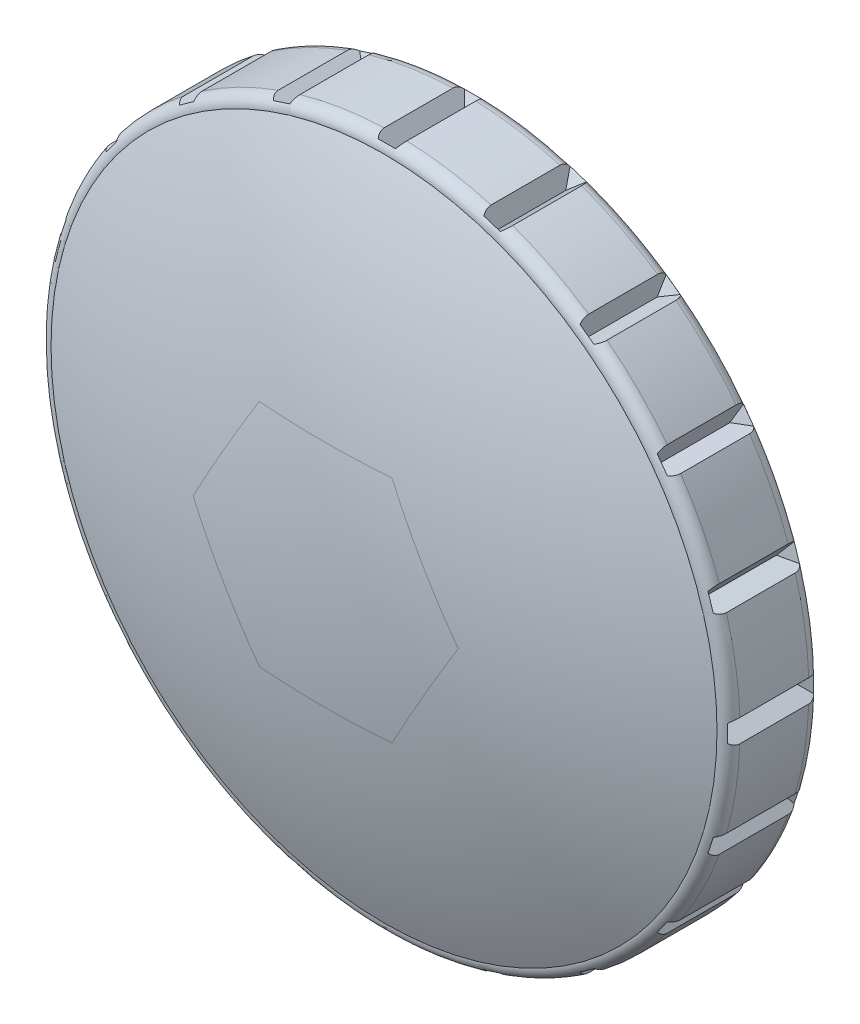
SolidWorks part; units mm, degrees
ref_plane "Front Plane" through (0, 0, 0) normal (0, 0, 1) x (1, 0, 0)
ref_plane "Top Plane" through (0, 0, 0) normal (0, 1, 0) x (1, 0, 0)
ref_plane "Right Plane" through (0, 0, 0) normal (1, 0, 0) x (0, 0, -1)
sketch "Sketch1" plane through (0, 0, 0) normal (0, 0, 1) x (1, 0, 0)
  circle A0 centre (0, 0) radius 38.1
  dimension "D1" = 76.2
extrude "Boss-Extrude1" add sketch "Sketch1" along normal mid plane 10.16
fillet "Fillet1" radius 1.27 2 edges at (38.1, 0, -5.08) (38.1, 0, 5.08)
ref_plane "Plane1" through (0, 38.1, 0) normal (0, 1, 0) x (1, 0, 0)
sketch "Sketch2" plane through (0, 38.1, 0) normal (0, 1, 0) x (1, 0, 0)
  line L0 (-36.83, -5.08) -> (36.83, -5.08) construction
  line L1 (-1.27, 5.08) -> (1.27, 5.08)
  line L2 (-1.27, 5.08) -> (-1.27, -5.08)
  line L3 (-1.27, -5.08) -> (1.27, -5.08)
  line L4 (1.27, 5.08) -> (1.27, -5.08)
  line L5 (-1.27, 5.08) -> (1.27, -5.08) construction
  line L6 (-1.27, -5.08) -> (1.27, 5.08) construction
  line L7 (36.83, 5.08) -> (-36.83, 5.08) construction
  point P0 (0, 0)
  dimension "D1" = 2.54
extrude "Cut-Extrude1" cut sketch "Sketch2" against normal blind 2.54 draft 35
pattern_circular "CirPattern1" count 20 over 360 about axis through (0, 0, 3.81) along (0, 0, -1) of "Cut-Extrude1"
dome "Dome1" faces to dome 1 distance 7.62 reverse direction no elliptical dome no face at (36.83, 0, 5.08) parameters "D1"=7.62
sketch "Sketch3" plane through (0, 0, -5.08) normal (0, 0, -1) x (-1, 0, 0)
  line L1 (30.7959, 0) -> (15.3979, 26.67)
  line L2 (15.3979, 26.67) -> (-15.3979, 26.67)
  line L3 (-15.3979, 26.67) -> (-30.7959, 0)
  line L4 (-30.7959, 0) -> (-15.3979, -26.67)
  line L5 (-15.3979, -26.67) -> (15.3979, -26.67)
  line L6 (15.3979, -26.67) -> (30.7959, 0)
  circle A0 centre (0, 0) radius 26.67 construction
  dimension "D1" = 53.34
extrude "Cut-Extrude2" cut sketch "Sketch3" against normal blind 2.54
sketch "Sketch5" plane through (0, 0, -2.54) normal (0, 0, -1) x (-1, 0, 0)
  line L0 (0, 7.6544) -> (0, -8.5734) construction
  line L1 (-14.6647, 0) -> (-7.3323, -12.7)
  line L2 (-7.3323, -12.7) -> (7.3323, -12.7)
  line L3 (7.3323, -12.7) -> (14.6647, 0)
  line L4 (14.6647, 0) -> (7.3323, 12.7)
  line L5 (7.3323, 12.7) -> (-7.3323, 12.7)
  line L6 (-7.3323, 12.7) -> (-14.6647, 0)
  line L7 (26.67, -25.4) -> (26.67, 25.4) construction
  line L8 (26.67, 25.4) -> (-26.67, 25.4) construction
  circle A0 centre (0, 0) radius 12.7 construction
  dimension "D1" = 25.4
split line "Split Line1"
